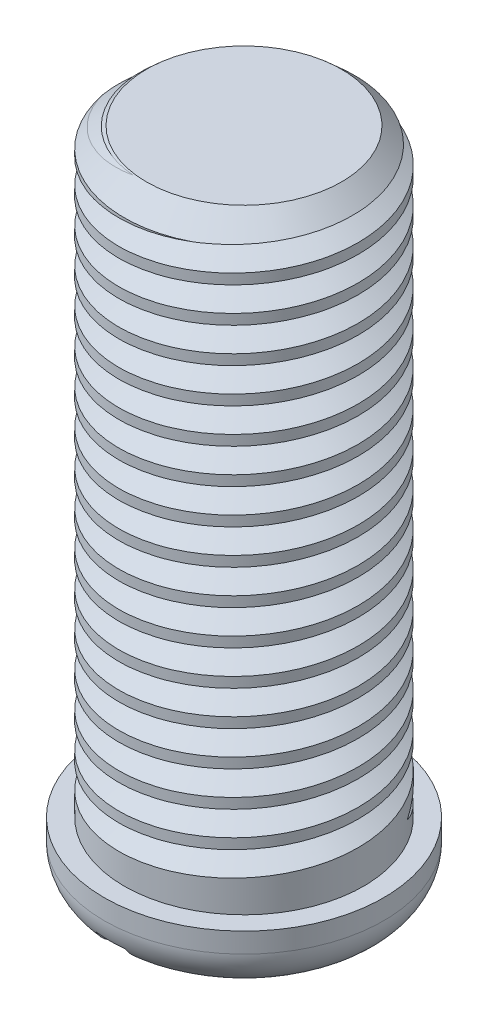
SolidWorks part; units mm, degrees
ref_plane "Alzado" through (0, 0, 0) normal (0, 0, 1) x (1, 0, 0)
ref_plane "Planta" through (0, 0, 0) normal (0, 1, 0) x (1, 0, 0)
ref_plane "Vista lateral" through (0, 0, 0) normal (1, 0, 0) x (0, 0, -1)
sketch "Croquis1" plane through (0, 0, 0) normal (0, 1, 0) x (1, 0, 0)
  circle A0 centre (0, 0) radius 7
  dimension "D1" = 14
extrude "Saliente-Extruir1" add sketch "Croquis1" along normal blind 3
sketch "Croquis2" plane through (0, 3, 0) normal (0, 1, 0) x (1, 0, 0)
  circle A0 centre (0, 0) radius 6
  dimension "D1" = 12
extrude "Saliente-Extruir2" add sketch "Croquis2" along normal blind 30
sketch "Croquis3" plane through (0, 3, 0) normal (0, 1, 0) x (1, 0, 0)
  circle A0 centre (0, 0) radius 6 construction
  circle A1 centre (0, 0) radius 6
sketch "Croquis4" plane through (0, 33, 0) normal (0, 1, 0) x (1, 0, 0)
  circle A0 centre (0, 0) radius 6 construction
  circle A1 centre (0, 0) radius 6
curve "Hélice/Espiral2" pitch 1.75 height 29 radius 6 centre (0, 33, 0) axis (0, -1, 0) start towards (0, 0, 1)
sketch "Croquis5" plane through (0, 0, 0) normal (1, 0, 0) x (0, 0, -1)
  line L1 (-4.93, 33) -> (-6.535, 33.9266)
  line L2 (-6.535, 33.9266) -> (-6.535, 32.0734)
  line L3 (-6.535, 32.0734) -> (-4.93, 33)
  circle A0 centre (-6, 33) radius 0.535 construction
  dimension "D1" = 1.07
chamfer "Chaflán1" distance 1 angle 48 1 edges at (0, 33, 6) first distance on face at (0, 33, 6)
sweep "Cortar-Barrer2" cut profiles "Croquis5" path "Hélice/Espiral2"
sketch "Croquis6" plane through (0, 0, 0) normal (-0.901, 0, -0.4339) x (-0.4339, 0, 0.901)
  line L3 (-6, 4.6174) -> (-6, 3.3821)
  line L4 (-6, 3.3821) -> (-4.93, 3.9997)
  line L5 (-4.93, 3.9997) -> (-6, 4.6174)
  line L6 (-6, 4.6174) -> (-6, 3.3821)
  line L7 (-6, 3.3821) -> (-4.93, 3.9997)
  line L8 (-4.93, 3.9997) -> (-6, 4.6174)
  dimension "D1" = 0
extrude "Cortar-Extruir1" cut sketch "Croquis6" against normal through all contours L6 L7 L8
sketch "Croquis8" plane through (0, 0, 0) normal (0, -1, 0) x (1, 0, 0)
  line L1 (0.75, -7.1594) -> (-0.75, -7.1594)
  line L2 (0.75, -7.1594) -> (0.75, 7.1594)
  line L3 (0.75, 7.1594) -> (-0.75, 7.1594)
  line L4 (-0.75, -7.1594) -> (-0.75, 7.1594)
  line L5 (0.75, -7.1594) -> (-0.75, 7.1594) construction
  line L6 (0.75, 7.1594) -> (-0.75, -7.1594) construction
  point P0 (0, 0)
  point P6 (0, 0)
  dimension "D1" = 1.5
fillet "Redondeo1" radius 2 1 edges at (0, 0, 7)
extrude "Cortar-Extruir2" cut sketch "Croquis8" against normal blind 1
